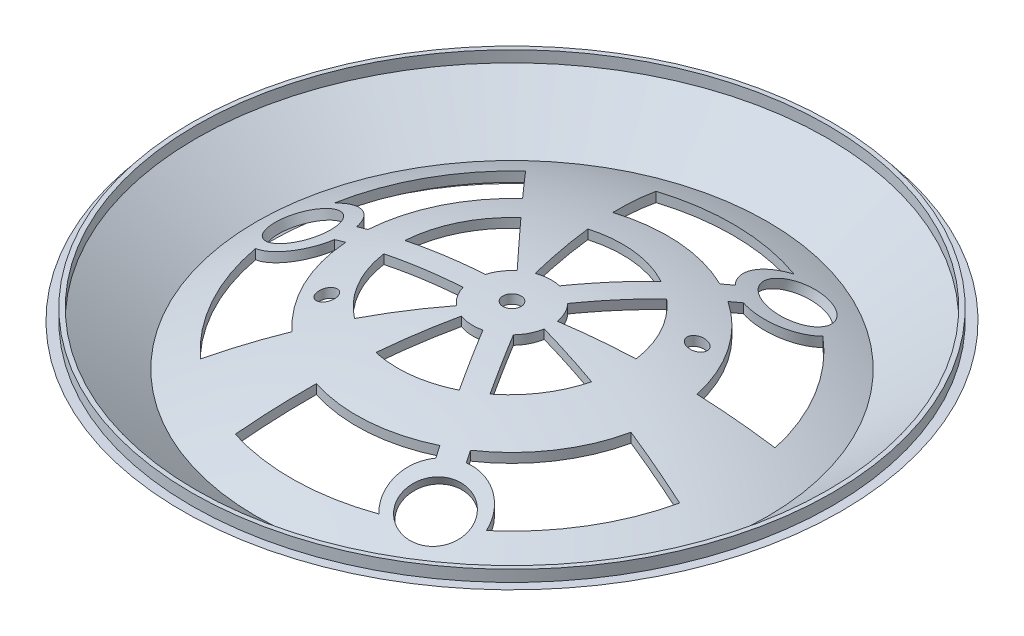
SolidWorks part; units mm, degrees
ref_plane "前视基准面" through (0, 0, 0) normal (0, 0, 1) x (1, 0, 0)
ref_plane "上视基准面" through (0, 0, 0) normal (0, 1, 0) x (1, 0, 0)
ref_plane "右视基准面" through (0, 0, 0) normal (1, 0, 0) x (0, 0, -1)
sketch "草图1" plane through (0, 0, 0) normal (0, 0, 1) x (1, 0, 0)
  line L0 (0, 0) -> (0, 192.4439) construction
  line L2 (-58.3077, 114.5097) -> (-56.0611, 113.3993)
  line L3 (0, 128.5) -> (0, 126.5)
  arc A0 (0, 126.5) -> (-56.0611, 113.3993) centre (0, 0) ccw
  arc A1 (0, 128.5) -> (-58.3077, 114.5097) centre (0, 0) ccw
  dimension "D1" = 126.5
  dimension "D2" = 128.5
revolve "旋转1" add sketch "草图1" angle 360 about L0
sketch "草图2" plane through (0, 0, 0) normal (0, 0, 1) x (1, 0, 0)
  line L0 (0, 0) -> (-58.7265, 152.9878) construction
  line L1 (-47.8502, 124.654) -> (-53.9651, 122.3067)
  line L2 (-53.9651, 122.3067) -> (-49.2451, 110.0105)
  line L3 (-49.2451, 110.0105) -> (-43.1301, 112.3579)
  line L4 (0, 0) -> (0, 153.4302) construction
  line L5 (-47.8502, 124.654) -> (-43.1301, 112.3579)
  dimension "D1" = 21
  dimension "D2" = 6.55
revolve "切除-旋转1" cut sketch "草图2" angle 360 about L0
pattern_circular "阵列(圆周)1" count 3 over 360 about axis through (0, 114.5097, 0) along (0, -1, 0) of "切除-旋转1"
sketch "草图3" plane through (0, 0, 0) normal (0, 1, 0) x (1, 0, 0)
  line L0 (-25.0445, -15.6968) -> (0, 0) construction
  line L1 (0, 0) -> (37.3499, 23.4093) construction
  line L2 (-12.5222, 19.9794) -> (10.9319, -17.4421) construction
  circle A0 centre (-25.0445, -15.6968) radius 2
  circle A1 centre (25.0445, 15.6968) radius 2
  dimension "D1" = 4
  dimension "D2" = 29.557
extrude "切除-拉伸1" cut sketch "草图3" along normal blind 169
sketch "草图4" plane through (0, 0, 0) normal (0, 1, 0) x (1, 0, 0)
  circle A0 centre (0, 0) radius 2
extrude "切除-拉伸2" cut sketch "草图4" along normal blind 169
sketch "草图6" plane through (0, 0, 0) normal (0, 0, 1) x (1, 0, 0)
  line L0 (-72.5, 124.7538) -> (-56.0611, 113.3993)
  line L1 (-56.0611, 113.3993) -> (-72.5, 113.3993)
  line L2 (-72.5, 113.3993) -> (-72.5, 124.7538)
  line L3 (0, 169.554) -> (0, 100.9628) construction
revolve "切除-旋转2" cut sketch "草图6" angle 360 about L3
sketch "草图7" plane through (0, 0, 0) normal (0, 0, 1) x (1, 0, 0)
  line L0 (56.0611, 113.3993) -> (72.5, 124.7538)
  line L1 (72.5, 124.7538) -> (70.5, 124.7538)
  line L2 (69.5, 124.7538) -> (53.0611, 113.3993)
  line L3 (56.0611, 113.3993) -> (-56.0611, 113.3993) construction
  line L4 (53.0611, 113.3993) -> (56.0611, 113.3993)
  line L5 (69.5, 124.7538) -> (69.5, 127.2538)
  line L6 (69.5, 127.2538) -> (70.5, 127.2538)
  line L7 (70.5, 127.2538) -> (70.5, 124.7538)
  line L8 (0, 167.4422) -> (0, 96.5473) construction
revolve "旋转2" add sketch "草图7" angle 360 about L8
sketch "草图8" plane through (0, 0, 0) normal (0, 1, 0) x (1, 0, 0)
  line L0 (4.3263, -7.4934) -> (11.2852, -19.5465) construction
  line L1 (8.5454, -1.4549) -> (22.1157, -4.6151)
  line L2 (-3.0127, -8.1279) -> (-7.3859, -22.5301)
  line L3 (20.4326, -30.4813) -> (19.1935, -28.3351)
  line L4 (16.1813, -32.9358) -> (14.9422, -30.7897)
  line L5 (-5.5326, -6.6731) -> (-16.372, -18.2525)
  line L6 (-5.5326, 6.6731) -> (-17.6427, 19.61)
  line L7 (-36.6139, -2.4545) -> (-34.1357, -2.4545)
  line L8 (-36.6139, 2.4545) -> (-34.1357, 2.4545)
  line L9 (-8.6527, 0) -> (-47.8716, 0) construction
  line L10 (-3.0127, 8.1279) -> (-8.0591, 24.7472)
  line L11 (8.5454, 1.4549) -> (22.5616, 4.7189)
  line L12 (16.1813, 32.9358) -> (14.9422, 30.7897)
  line L13 (20.4326, 30.4813) -> (19.1935, 28.3351)
  line L14 (-10.4412, 32.5922) -> (-14.598, 46.2818)
  line L15 (-23.0051, -25.3385) -> (-32.7822, -35.7831)
  line L16 (-25.7492, -2.4545) -> (-8.3136, -2.4545)
  line L17 (-25.9911, 2.4545) -> (-8.3136, 2.4545)
  line L18 (-23.0051, 25.3385) -> (-32.7822, 35.7831)
  line L19 (-10.4412, -32.5922) -> (-14.598, -46.2818)
  line L20 (9.1375, -20.7357) -> (2.0311, -8.427)
  line L21 (17.1119, -29.6387) -> (23.9358, -41.458) construction
  line L22 (13.309, -18.1428) -> (6.2825, -5.9725)
  line L23 (33.4463, -7.2538) -> (47.3802, -10.4987)
  line L24 (33.4463, 7.2538) -> (47.3802, 10.4987)
  line L25 (14.2492, 19.7713) -> (6.2825, 5.9725)
  line L26 (17.1119, 29.6387) -> (23.9358, 41.458) construction
  line L27 (10.1992, 22.5745) -> (2.0311, 8.427)
  line L28 (4.3263, 7.4934) -> (12.2866, 21.2811) construction
  arc A0 (-14.598, -46.2818) -> (16.3833, -45.6803) centre (0, 0) ccw
  arc A1 (31.3686, -37.0285) -> (20.4326, -30.4813) centre (22.6364, -39.2073) ccw
  arc A2 (31.3686, -37.0285) -> (47.3802, -10.4987) centre (0, 0) ccw
  arc A3 (-32.7822, 35.7831) -> (-47.752, 8.6518) centre (0, 0) ccw
  arc A4 (-47.752, -8.6518) -> (-36.6139, -2.4545) centre (-45.2727, 0) ccw
  arc A5 (-47.752, -8.6518) -> (-32.7822, -35.7831) centre (0, 0) ccw
  arc A6 (-5.5326, 6.6731) -> (-8.3136, 2.4545) centre (0, 0) ccw
  arc A7 (47.3802, 10.4987) -> (31.3686, 37.0285) centre (0, 0) ccw
  arc A8 (16.3833, 45.6803) -> (16.1813, 32.9358) centre (22.6364, 39.2073) ccw
  arc A9 (16.3833, 45.6803) -> (-14.598, 46.2818) centre (0, 0) ccw
  arc A10 (8.5454, 1.4549) -> (6.2825, 5.9725) centre (0, 0) ccw
  arc A11 (-3.0127, -8.1279) -> (2.0311, -8.427) centre (0, 0) ccw
  arc A12 (6.2825, -5.9725) -> (8.5454, -1.4549) centre (0, 0) ccw
  arc A13 (-8.3136, -2.4545) -> (-5.5326, -6.6731) centre (0, 0) ccw
  arc A14 (2.0311, 8.427) -> (-3.0127, 8.1279) centre (0, 0) ccw
  arc A15 (-36.6139, 2.4545) -> (-47.752, 8.6518) centre (-45.2727, 0) ccw
  arc A16 (20.4326, 30.4813) -> (31.3686, 37.0285) centre (22.6364, 39.2073) ccw
  arc A17 (16.1813, -32.9358) -> (16.3833, -45.6803) centre (22.6364, -39.2073) ccw
  arc A18 (-23.0051, 25.3385) -> (-34.1357, 2.4545) centre (0, 0) ccw
  arc A19 (-17.6427, 19.61) -> (-25.9911, 2.4545) centre (-1.6032, 1.1957) ccw
  circle A20 centre (0, 0) radius 2 construction
  arc A21 (-10.4412, -32.5922) -> (14.9422, -30.7897) centre (0, 0) ccw
  arc A22 (-7.3859, -22.5301) -> (9.1375, -20.7357) centre (-1.6032, 1.1957) ccw
  arc A23 (-34.1357, -2.4545) -> (-23.0051, -25.3385) centre (0, 0) ccw
  arc A24 (-25.7492, -2.4545) -> (-16.372, -18.2525) centre (-1.6032, 1.1957) ccw
  arc A25 (13.309, -18.1428) -> (22.1157, -4.6151) centre (-1.6032, 1.1957) ccw
  arc A26 (19.1935, -28.3351) -> (33.4463, -7.2538) centre (0, 0) ccw
  arc A27 (33.4463, 7.2538) -> (19.1935, 28.3351) centre (0, 0) ccw
  arc A28 (22.5616, 4.7189) -> (14.2492, 19.7713) centre (-1.6032, 1.1957) ccw
  arc A29 (10.1992, 22.5745) -> (-8.0591, 24.7472) centre (-1.6032, 1.1957) ccw
  arc A30 (14.9422, 30.7897) -> (-10.4412, 32.5922) centre (0, 0) ccw
  point P23 (0, 0)
  point P27 (0, 0)
  point P43 (0, 0)
  point P46 (0, 0)
  dimension "D1" = 3
extrude "切除-拉伸4" cut sketch "草图8" along normal blind 354
equation "\"13.1、2\"=2.64861"
